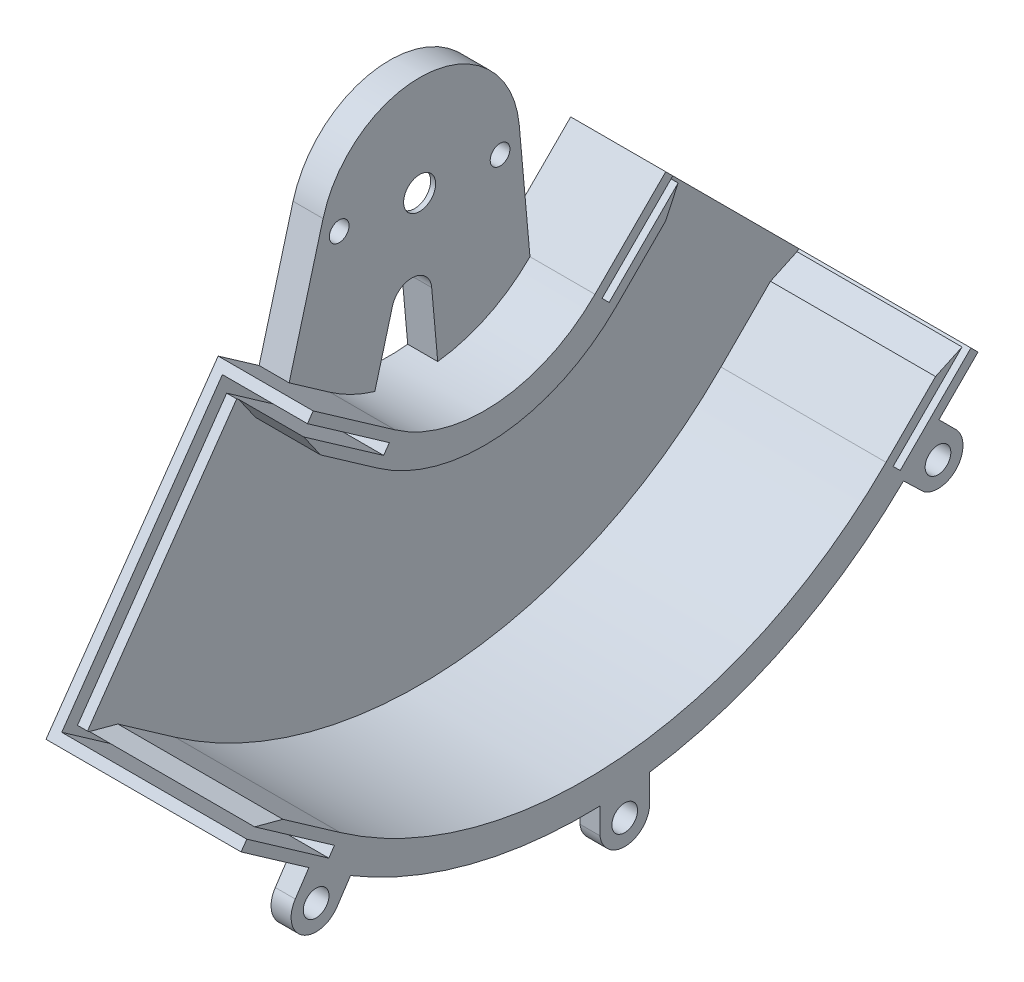
SolidWorks part; units mm, degrees
ref_plane "Front Plane" through (0, 0, 0) normal (0, 0, 1) x (1, 0, 0)
ref_plane "Top Plane" through (0, 0, 0) normal (0, 1, 0) x (1, 0, 0)
ref_plane "Right Plane" through (0, 0, 0) normal (1, 0, 0) x (0, 0, -1)
sketch "Sketch3" plane through (0, 0, 0) normal (1, 0, 0) x (0, 0, -1)
  line L0 (-22.7274, -32.4581) -> (-62.0633, -88.6355)
  line L1 (28.0184, -28.0184) -> (76.5118, -76.5118)
  line L2 (-22.7274, -32.4581) -> (0, 0) construction
  line L3 (0, 0) -> (28.0184, -28.0184) construction
  line L4 (0, 40.513) -> (0, -40.513) construction
  line L5 (-62.0633, -88.6355) -> (-66.4339, -94.8775)
  line L6 (76.5118, -76.5118) -> (81.8999, -81.8999)
  arc A2 (-62.0633, -88.6355) -> (76.5118, -76.5118) centre (0, 0) ccw
  arc A4 (-27.098, -38.7) -> (33.4066, -33.4066) centre (0, 0) ccw
  arc A5 (-22.7274, -32.4581) -> (28.0184, -28.0184) centre (0, 0) ccw
  arc A6 (-66.4339, -94.8775) -> (81.8999, -81.8999) centre (0, 0) ccw
  dimension "D1" = 216.408
  dimension "D2" = 135
  dimension "D3" = 94.488
  dimension "D4" = 7.62
  dimension "D6" = 7.62
  dimension "D5" = 80
extrude "Base extrude" add sketch "Sketch3" along normal blind 58.42 contours L5 A6 L6 A2 | A5 L0 A4 L1 region at (0, -39.9408, -3.4944) region at (0, -109.321, -9.5643)
sketch "Sketch4" plane through (58.42, 0, 0) normal (1, 0, 0) x (0, 0, -1)
  line L0 (-66.4339, -94.8775) -> (-22.7274, -32.4581)
  line L1 (28.0184, -28.0184) -> (81.8999, -81.8999)
  arc A0 (-22.7274, -32.4581) -> (28.0184, -28.0184) centre (0, 0) ccw
  arc A1 (-22.7274, -32.4581) -> (28.0184, -28.0184) centre (0, 0) ccw construction
  arc A2 (-66.4339, -94.8775) -> (81.8999, -81.8999) centre (0, 0) ccw
  arc A3 (-66.4339, -94.8775) -> (81.8999, -81.8999) centre (0, 0) ccw construction
  arc M1 (28.0184, -28.0184) -> (-22.7274, -32.4581) centre (0, 0) cw
  line M2 (-22.7274, -32.4581) -> (-27.098, -38.7)
  arc M3 (-27.098, -38.7) -> (33.4066, -33.4066) centre (0, 0) ccw
  line M4 (33.4066, -33.4066) -> (28.0184, -28.0184)
extrude "Outer wall" add sketch "Sketch4" along normal blind 7.62 contours L0 A2 L1 M3 | M4 M1 M2 M3 region at (58.42, -79.1939, -6.9286) region at (58.42, -39.9408, -3.4944)
ref_plane "Midplane" through (29.21, 0, 0) normal (-1, 0, 0) x (0, 0, 1)
mirror "Mirror1" about plane through (29.21, 0, 0) normal (-1, 0, 0) of "Outer wall"
sketch "Sketch6" plane through (0, 0, 0) normal (0, 0.5736, 0.8192) x (1, 0, 0)
  line L27 (-5.08, -42.164) -> (63.5, -42.164)
  line L28 (-5.08, -42.164) -> (-5.08, -113.284)
  line L29 (-5.08, -113.284) -> (63.5, -113.284)
  line L30 (63.5, -42.164) -> (63.5, -113.284)
  line L31 (-2.54, -44.704) -> (60.96, -44.704)
  line L32 (-2.54, -44.704) -> (-2.54, -110.744)
  line L33 (-2.54, -110.744) -> (60.96, -110.744)
  line L34 (60.96, -44.704) -> (60.96, -110.744)
  line L35 (58.42, -47.244) -> (0, -47.244) construction
  line L36 (0, -108.204) -> (0, -18.7894) construction
  line L37 (58.42, -18.7894) -> (58.42, -108.204) construction
  line L38 (58.42, -108.204) -> (0, -108.204) construction
  line L40 (0, -47.244) -> (58.42, -47.244)
  line L41 (0, -47.244) -> (0, -108.204)
  line L42 (0, -108.204) -> (58.42, -108.204)
  line L43 (58.42, -47.244) -> (58.42, -108.204)
  line L44 (-7.62, -39.624) -> (66.04, -39.624)
  line L45 (-7.62, -39.624) -> (-7.62, -115.824)
  line L46 (-7.62, -115.824) -> (66.04, -115.824)
  line L47 (66.04, -39.624) -> (66.04, -115.824)
  line M21 (-7.62, -39.624) -> (-7.62, -115.824)
  line M22 (-7.62, -115.824) -> (66.04, -115.824)
  line M23 (66.04, -115.824) -> (66.04, -39.624)
  line M24 (66.04, -39.624) -> (-7.62, -39.624)
  line M25 (58.42, -108.204) -> (0, -108.204)
  line M26 (0, -108.204) -> (0, -47.244)
  line M27 (0, -47.244) -> (58.42, -47.244)
  line M28 (58.42, -47.244) -> (58.42, -108.204)
  dimension "D1" = 2.54
  dimension "D2" = 2.54
  dimension "D3" = 2.54
  dimension "D4" = 2.54
  dimension "D5" = 2.54
  dimension "D6" = 2.54
  dimension "D7" = 2.54
  dimension "D8" = 2.54
extrude "Endcap 1" add sketch "Sketch6" along normal blind 25.4 contours L27 L30 L29 L28 M24 M21 M22 M23 | L34 L31 L32 L33 M28 M25 M26 M27 region at (29.21, -37.3698, 26.1667) region at (29.21, -33.3262, 23.3353)
sketch "Sketch7" plane through (0, 0, 0) normal (0, 0.7071, -0.7071) x (1, 0, 0)
  line L0 (-5.08, 113.284) -> (63.5, 113.284)
  line L1 (-5.08, 113.284) -> (-5.08, 42.164)
  line L2 (-5.08, 42.164) -> (63.5, 42.164)
  line L3 (63.5, 113.284) -> (63.5, 42.164)
  line L4 (-2.54, 110.744) -> (60.96, 110.744)
  line L5 (-2.54, 110.744) -> (-2.54, 44.704)
  line L6 (-2.54, 44.704) -> (60.96, 44.704)
  line L7 (60.96, 110.744) -> (60.96, 44.704)
  line L8 (0, 108.204) -> (58.42, 108.204)
  line L9 (0, 108.204) -> (0, 47.244)
  line L10 (0, 47.244) -> (58.42, 47.244)
  line L11 (58.42, 108.204) -> (58.42, 47.244)
  line L12 (-7.62, 115.824) -> (66.04, 115.824)
  line L13 (-7.62, 115.824) -> (-7.62, 39.624)
  line L14 (-7.62, 39.624) -> (66.04, 39.624)
  line L15 (66.04, 115.824) -> (66.04, 39.624)
  line L16 (58.42, 108.204) -> (0, 108.204) construction
  line L17 (58.42, 47.244) -> (58.42, 108.204) construction
  line L18 (66.04, 115.824) -> (-7.62, 115.824) construction
  line L19 (66.04, 39.624) -> (66.04, 115.824) construction
  line L20 (-7.62, 39.624) -> (-7.62, 115.824) construction
  line L21 (66.04, 39.624) -> (-7.62, 39.624) construction
  line M17 (66.04, 115.824) -> (-7.62, 115.824)
  line M18 (-7.62, 115.824) -> (-7.62, 39.624)
  line M19 (-7.62, 39.624) -> (66.04, 39.624)
  line M20 (66.04, 39.624) -> (66.04, 115.824)
  line M21 (0, 47.244) -> (0, 108.204)
  line M22 (0, 108.204) -> (58.42, 108.204)
  line M23 (58.42, 108.204) -> (58.42, 47.244)
  line M24 (58.42, 47.244) -> (0, 47.244)
  dimension "D1" = 2.54
  dimension "D2" = 2.54
  dimension "D3" = 2.54
  dimension "D4" = 2.54
  dimension "D5" = 2.54
  dimension "D6" = 2.54
  dimension "D7" = 2.54
  dimension "D8" = 2.54
extrude "Endcap 2" add sketch "Sketch7" along normal blind 25.4 contours L0 L3 L2 L1 M20 M17 M18 M19 | L7 L4 L5 L6 M24 M21 M22 M23 region at (29.21, -77.66, -77.66) region at (29.21, -81.1505, -81.1505)
chamfer "Internal Chamfer" distance 7.62 angle 20 4 edges at (29.21, -74.0667, 82.8697) (29.21, -24.1312, 47.9045) (29.21, -58.5513, -94.4723) (29.21, -15.446, -51.3671) first distance on face at (29.21, -81.3511, 72.4665) first distance on face at (29.21, -31.4156, 37.5013) first distance on face at (29.21, -67.5315, -85.492) first distance on face at (29.21, -24.4263, -42.3868)
ref_plane "Plane2" through (0, -13.9736, -1.2225) normal (0, -0.9962, -0.0872) x (-1, 0, 0)
sketch "Sketch10" plane through (0, -13.9736, -1.2225) normal (0, -0.9962, -0.0872) x (-1, 0, 0)
  line L0 (-66.04, 93.9078) -> (7.62, 93.9078) construction
  line L1 (-16.51, 95.5358) -> (-41.91, 95.5358)
  line L2 (-16.51, 95.5358) -> (-16.51, -82.1857)
  line L3 (-16.51, -82.1857) -> (-41.91, -82.1857)
  line L4 (-41.91, 95.5358) -> (-41.91, -82.1857)
  point P4 (-29.21, 93.9078)
  point P5 (-29.21, 95.5358)
  dimension "D1" = 25.4
extrude "Flywheel Hole" cut sketch "Sketch10" along normal up to next
sketch "Sketch11" plane through (-7.62, 0, 0) normal (-1, 0, 0) x (0, 0, 1)
  line L0 (-25.2982, 2.2719) -> (-28.0184, -28.0184)
  line L4 (-3.0636, -22.3183) -> (-4.5937, -39.3568)
  line L5 (6.8995, -21.445) -> (11.3704, -37.9575)
  line L6 (-20.4217, -1.79) -> (20.4217, 1.79) construction
  line L7 (24.5172, 6.6383) -> (33.1306, -25.1737)
  line L8 (43.5339, -17.8892) -> (22.7274, -32.4581) construction
  line L10 (1.5525, -17.7121) -> (-2.2178, 25.303) construction
  line L11 (22.7274, -32.4581) -> (43.5339, -17.8892)
  line L12 (22.7274, -32.4581) -> (33.1306, -25.1737)
  arc A1 (-28.0184, -28.0184) -> (22.7274, -32.4581) centre (0, 0) ccw construction
  circle A3 centre (0, 0) radius 4.064
  arc A4 (24.5172, 6.6383) -> (-25.2982, 2.2719) centre (0, 0) ccw
  circle A6 centre (-20.4217, -1.79) radius 2.5
  circle A7 centre (20.4217, 1.79) radius 2.5
  arc A8 (-3.0636, -22.3183) -> (6.8995, -21.445) centre (1.9961, -22.7727) cw
  arc A11 (11.3704, -37.9575) -> (22.7274, -32.4581) centre (0, 0) ccw
  arc A12 (-28.0184, -28.0184) -> (22.7274, -32.4581) centre (0, 0) ccw
  arc A13 (-28.0184, -28.0184) -> (-4.5937, -39.3568) centre (0, 0) ccw
  point P22 (0, 0)
  dimension "D3" = 8.128
  dimension "D2" = 25.4
  dimension "D1" = 5
  dimension "D5" = 5.08
  dimension "D4" = 41
  dimension "D7" = 43.18
  dimension "D6" = 0
extrude "Flywheel holder" add sketch "Sketch11" against normal blind 7.62
sketch "Sketch12" plane through (-7.62, 0, 0) normal (-1, 0, 0) x (0, 0, 1)
  circle A0 centre (0, 0) radius 14.605
  dimension "D1" = 29.21
extrude "Motor insert" cut sketch "Sketch12" against normal blind 6.35
sketch "Sketch13" plane through (66.04, 0, 0) normal (1, 0, 0) x (0, 0, -1)
  line L1 (-110.5367, 4.1813) -> (110.9716, 4.1813)
  line L2 (-110.5367, 4.1813) -> (-110.5367, -123.3274)
  line L3 (-110.5367, -123.3274) -> (110.9716, -123.3274)
  line L4 (110.9716, 4.1813) -> (110.9716, -123.3274)
extrude "Cut-Extrude1" cut sketch "Sketch13" against normal up to surface (24.13 mm away) up to face at (41.91, -26.9401, -2.3569)
sketch "Sketch14" plane through (41.91, 0, 0) normal (1, 0, 0) x (0, 0, -1)
  line L0 (-73.4762, -97.5482) -> (-70.0245, -92.3633)
  line L1 (-66.4339, -94.8775) -> (-87.2404, -80.3086) construction
  line L2 (-70.0245, -92.3633) -> (-59.4528, -99.401)
  line L3 (-59.4528, -99.401) -> (-62.9045, -104.586)
  line L4 (3.8593, -122.286) -> (3.8593, -115.7597)
  line L5 (3.8593, -115.7597) -> (16.51, -114.6413)
  line L6 (16.51, -114.6413) -> (16.51, -121.4959)
  line L7 (86.1731, -87.8533) -> (80.953, -82.836)
  line L8 (80.953, -82.836) -> (89.843, -73.7664)
  line L10 (89.843, -73.7664) -> (94.5478, -78.4712)
  line L11 (99.8604, -63.9394) -> (81.8999, -81.8999) construction
  circle A0 centre (-68.1904, -101.0671) radius 3.2639
  circle A1 centre (89.7004, -82.5731) radius 3.2639
  circle A2 centre (10.16, -121.4959) radius 3.2639
  arc A3 (-73.4762, -97.5482) -> (-62.9045, -104.586) centre (-68.1904, -101.0671) ccw
  arc A4 (3.8593, -122.286) -> (16.51, -121.4959) centre (10.16, -121.4959) ccw
  arc A5 (86.1731, -87.8533) -> (93.8023, -77.7257) centre (89.7004, -82.5731) ccw
  arc A6 (-66.4339, -94.8775) -> (81.8999, -81.8999) centre (0, 0) ccw construction
  point P13 (3.8325, -115.7606)
  line M9 (-87.2404, -80.3086) -> (-66.4339, -94.8775)
  arc M10 (-66.4339, -94.8775) -> (81.8999, -81.8999) centre (0, 0) ccw
  line M11 (81.8999, -81.8999) -> (99.8604, -63.9394)
  dimension "D7" = 6.5278
  dimension "D8" = 12.7
  dimension "D1" = 121.92
  dimension "D2" = 121.92
  dimension "D3" = 19.05
  dimension "D4" = 10.16
  dimension "D5" = 121.92
  dimension "D6" = 10.16
  dimension "D9" = 12.7
  dimension "D10" = 12.7
  dimension "D11" = 12.7
extrude "Boss-Extrude1" add sketch "Sketch14" against normal blind 5.08 contours L7 A5 L10 A1 M11 M10 | L0 A3 L3 A0 M10 M9 | L5 L6 A4 L4 | A2 region at (41.91, -82.521, -81.5777) region at (41.91, -95.0739, 71.573)
